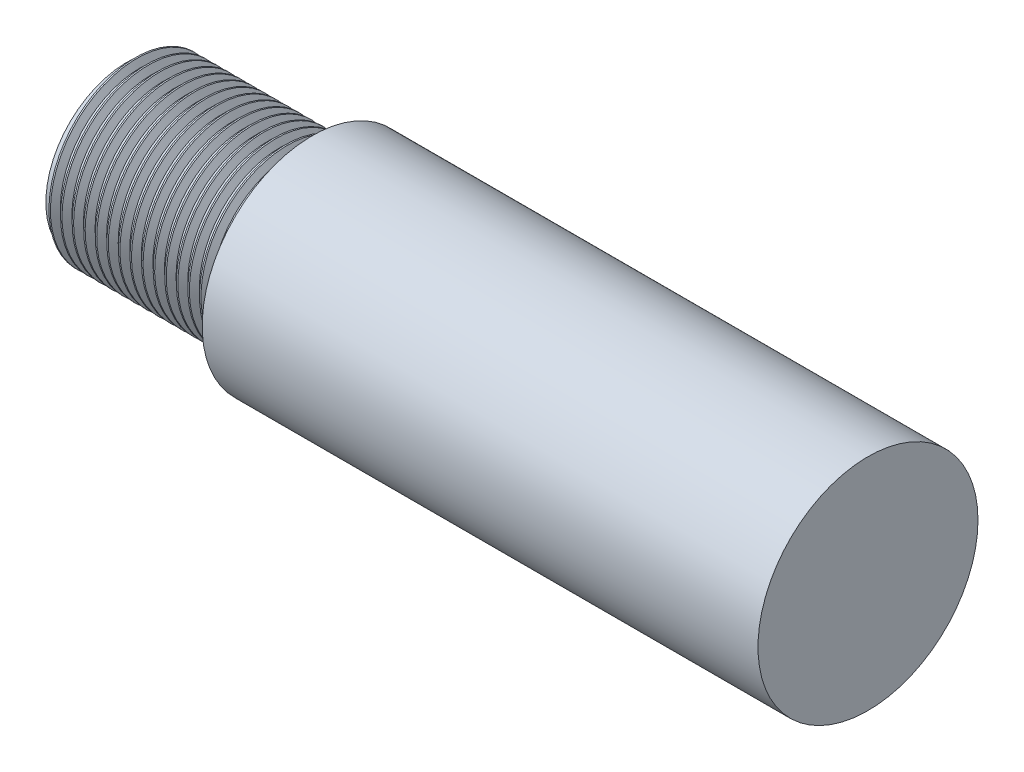
SolidWorks part; units mm, degrees
ref_plane "Front Plane" through (0, 0, 0) normal (0, 0, 1) x (1, 0, 0)
ref_plane "Top Plane" through (0, 0, 0) normal (0, 1, 0) x (1, 0, 0)
ref_plane "Right Plane" through (0, 0, 0) normal (1, 0, 0) x (0, 0, -1)
sketch "Sketch1" plane through (0, 0, 0) normal (1, 0, 0) x (0, 0, -1)
  circle A0 centre (0, 0) radius 2.375
  dimension "D1" = 4.75
extrude "Boss-Extrude1" add sketch "Sketch1" along normal blind 12
sketch "Sketch2" plane through (0, 0, 0) normal (-1, 0, 0) x (0, 0, 1)
  circle A0 centre (0, 0) radius 1.75
  dimension "D1" = 3.5
extrude "Boss-Extrude2" add sketch "Sketch2" along normal blind 4
thread "Thread1" pitch 0.25 method extrude profile "Thread Profile1" start angle 0, offset 0, length 0, pitch 0.25, diameter 3.5
ref_plane "Plane1" through (-4, 0, -1.75) normal (0, -1, 0) x (0, 0, -1)
sketch "Thread Profile1" plane through (-4, 0, -1.75) normal (0, -1, 0) x (0, 0, -1)
  line L0 (0, 0) -> (0, 0.25) construction
  line L1 (0, 0) -> (0.1353, 0.0781)
  line L2 (0.1353, 0.0781) -> (0.1353, 0.1094)
  line L3 (0.1353, 0.1094) -> (0, 0.1875)
  line L4 (0.1353, 0.0937) -> (0, 0.0937) construction
  line L11 (0, 0) -> (0, 0.1875)
  point P2 (0, 0)
  dimension "Pitch" = 0.25
  dimension "Profile_Angle" = 60
  dimension "Profile_Land" = 0.0312
  dimension "Profile_Height" = 0.1353
